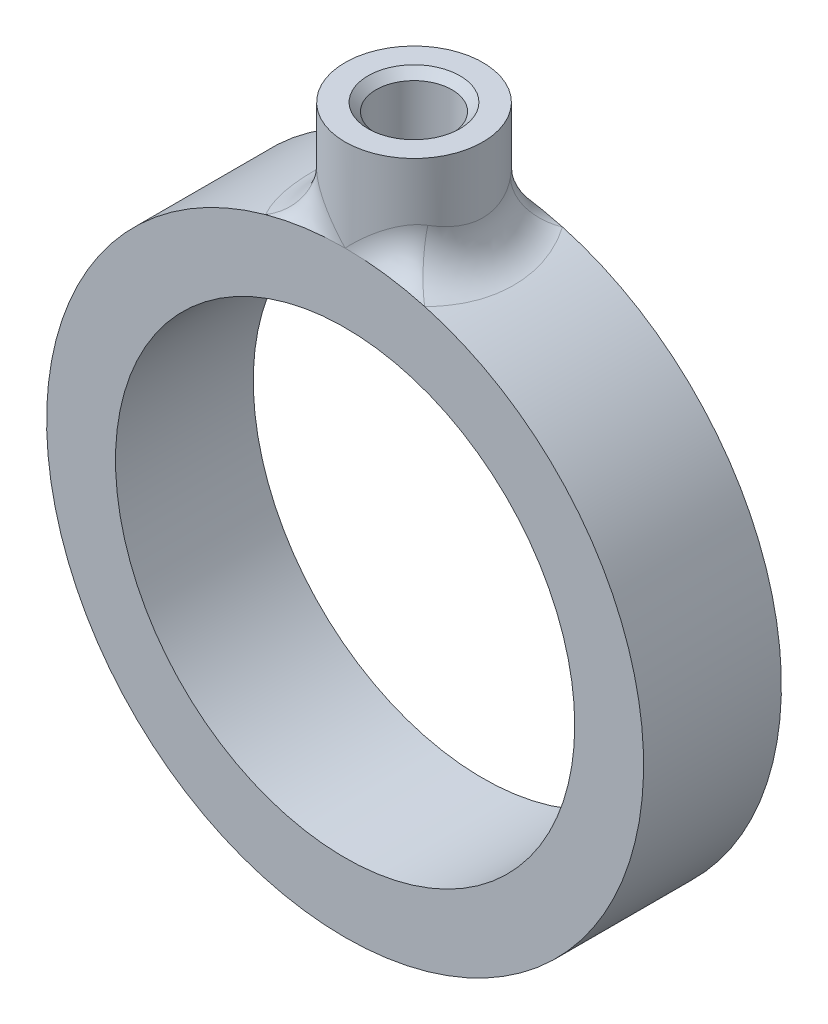
SolidWorks part; units mm, degrees
ref_plane "Front Plane" through (0, 0, 0) normal (0, 0, 1) x (1, 0, 0)
ref_plane "Top Plane" through (0, 0, 0) normal (0, 1, 0) x (1, 0, 0)
ref_plane "Right Plane" through (0, 0, 0) normal (1, 0, 0) x (0, 0, -1)
sketch "Sketch1" plane through (0, 0, 0) normal (0, 0, 1) x (1, 0, 0)
  circle A0 centre (0, 0) radius 13
  circle A1 centre (0, 0) radius 10
  dimension "D1" = 26
  dimension "D2" = 20
extrude "Boss-Extrude1" add sketch "Sketch1" along normal mid plane 6
sketch "Sketch2" plane through (0, 0, 0) normal (0, 1, 0) x (1, 0, 0)
  circle A0 centre (0, 0) radius 3
  dimension "D1" = 6
extrude "Boss-Extrude2" add sketch "Sketch2" against normal up to next from offset 17
fillet "Fillet1" radius 2 2 edges at (-2.9196, 12.6679, 0.69) (2.9196, 12.6679, 0.69)
hole_wizard "M4 Tapped Hole1" positions "Sketch3" profile "Sketch4" tap size "M4" standard "ISO"
sketch "Sketch3" plane through (0, 17, 0) normal (0, 1, 0) x (1, 0, 0)
  point P0 (0, 0)
sketch "Sketch4" plane through (0, 17, 0) normal (1, 0, 0) x (0, 0, 1)
  line L0 (0, 0) -> (0, 12.9914)
  line L1 (0, 12.9914) -> (1.65, 12)
  line L2 (1.65, 12) -> (1.65, 0.35)
  line L3 (1.65, 0.35) -> (2, 0)
  line L5 (2, 0) -> (0, 0)
  line L6 (-1.65, 0.35) -> (-2, 0) construction
  line L10 (0, 12.9914) -> (-1.65, 12) construction
  line L11 (0, -6.35) -> (0, 107.95) construction
  dimension "Tap Drill Dia." = 3.3
  dimension "Tap Drill Depth" = 12
  dimension "Near C'Sink Dia." = 4
  dimension "Near C'Sink Angle" = 90
  dimension "Drill Angle" = 118
cosmetic thread "Hole Thread1" parameters "D1"=7.1371, "D2"=4
